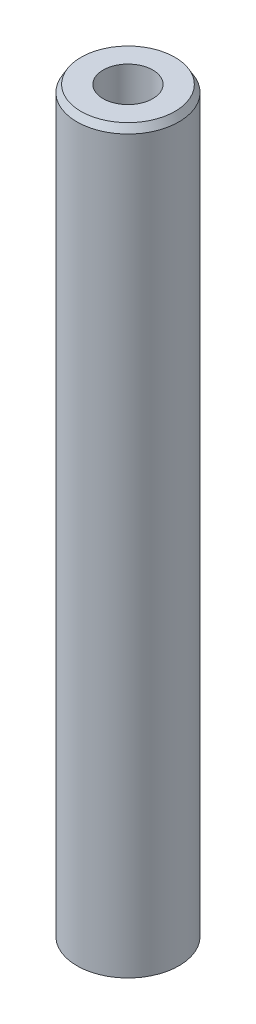
SolidWorks part; units mm, degrees
ref_plane "Front Plane" through (0, 0, 0) normal (0, 0, 1) x (1, 0, 0)
ref_plane "Top Plane" through (0, 0, 0) normal (0, 1, 0) x (1, 0, 0)
ref_plane "Right Plane" through (0, 0, 0) normal (1, 0, 0) x (0, 0, -1)
sketch "Sketch1" plane through (0, 0, 0) normal (0, 1, 0) x (1, 0, 0)
  circle A0 centre (0, 0) radius 7.5
  dimension "SHAFT_OD" = 15
extrude "Boss-Extrude1" add sketch "Sketch1" along normal blind 109.1037
sketch "Sketch2" plane through (0, 0, 0) normal (0, 1, 0) x (1, 0, 0)
  circle A0 centre (0, 0) radius 3.6534
  dimension "BORE_D" = 7.3069
extrude "Cut-Extrude1" cut sketch "Sketch2" along normal through all
chamfer "Chamfer1" distance 1.0325 angle 30 2 edges at (0, 109.1037, 7.5) (0, 0, 7.5) first distance on face at (0, 109.1037, 7.5) first distance on face at (0, 0, 3.6534)
